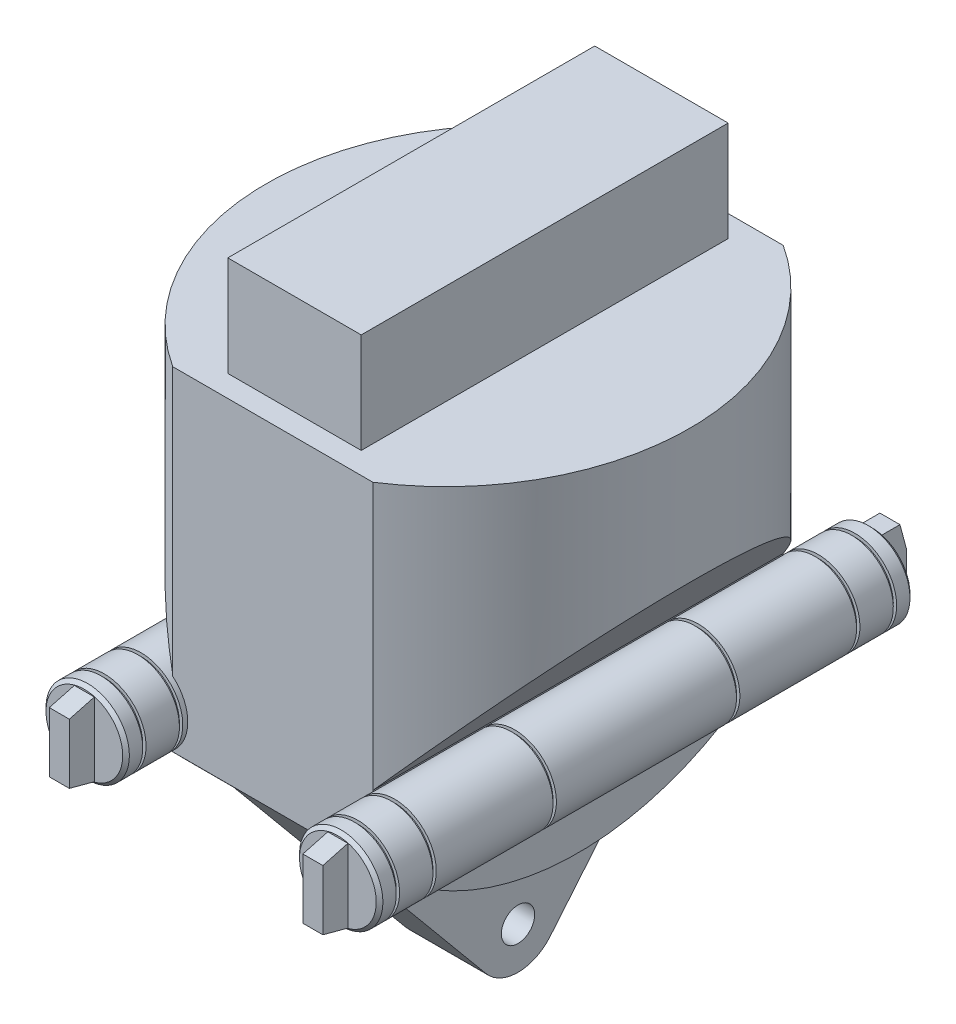
SolidWorks part; units mm, degrees
ref_plane "Front Plane" through (0, 0, 0) normal (0, 0, 1) x (1, 0, 0)
ref_plane "Top Plane" through (0, 0, 0) normal (0, 1, 0) x (1, 0, 0)
ref_plane "Right Plane" through (0, 0, 0) normal (1, 0, 0) x (0, 0, -1)
sketch "Sketch1" plane through (0, 0, 0) normal (1, 0, 0) x (0, 0, -1)
  line L1 (-61.5, 83.5) -> (61.5, 83.5)
  line L2 (-61.5, 83.5) -> (-61.5, -83.5)
  line L3 (-61.5, -83.5) -> (61.5, -83.5)
  line L4 (61.5, 83.5) -> (61.5, -83.5)
  line L5 (-61.5, 83.5) -> (61.5, -83.5) construction
  line L6 (-61.5, -83.5) -> (61.5, 83.5) construction
  point P0 (0, 0)
  dimension "D1" = 123
  dimension "D2" = 167
extrude "Boss-Extrude1" add sketch "Sketch1" along normal mid plane 127
sketch "Sketch2" plane through (0, 83.5, 0) normal (0, 1, 0) x (1, 0, 0)
  line L0 (0, 61.5) -> (0, -61.5) construction
  line L1 (63.5, 61.5) -> (-63.5, 61.5) construction
  line L2 (63.5, -61.5) -> (-63.5, -61.5) construction
  line L3 (-30, 61.5) -> (-30, -61.5) construction
  line L4 (-30, 61.5) -> (-63.5, 61.5)
  line L5 (-63.5, 61.5) -> (-63.5, -61.5)
  line L6 (-63.5, -61.5) -> (-30, -61.5)
  line L7 (63.5, -61.5) -> (30, -61.5)
  line L8 (30, 61.5) -> (63.5, 61.5)
  line L9 (63.5, 61.5) -> (63.5, -61.5)
  arc A0 (-30, 61.5) -> (-30, -61.5) centre (9.7015, 0) ccw
  arc A1 (30, 61.5) -> (30, -61.5) centre (-9.7015, 0) cw
  line M6 (-63.5, 61.5) -> (-63.5, -61.5)
  line M7 (-63.5, -61.5) -> (63.5, -61.5)
  line M8 (63.5, -61.5) -> (63.5, 61.5)
  line M9 (63.5, 61.5) -> (-63.5, 61.5)
  dimension "D2" = 73.2015
  dimension "D1" = 30
extrude "Cut-Extrude1" cut sketch "Sketch2" against normal through all contours A0 M9 M6 | A0 L5 M7 | A1 M8 M7 | A1 L9 M9 region at (-54.0203, 83.5, -46.9159) region at (-54.0203, 83.5, 46.9159) region at (54.0203, 83.5, -46.9159) region at (54.0203, 83.5, 46.9159)
sketch "Sketch3" plane through (0, 0, 61.5) normal (0, 0, 1) x (1, 0, 0)
  line L0 (0, 83.5) -> (0, -83.5) construction
  line L3 (30, 83.5) -> (-30, 83.5) construction
  line L4 (-12, -83.5) -> (-12, -43.5)
  line L5 (-12, -43.5) -> (-30, -43.5)
  line L6 (-30, -83.5) -> (-30, 83.5) construction
  line L7 (30, -83.5) -> (-30, -83.5) construction
  line L8 (-12, -83.5) -> (0, -83.5) construction
  line L9 (-30, -43.5) -> (-30, 3.5)
  line L10 (-30, 3.5) -> (-63.5, 43.5)
  line L11 (-63.5, 83.5) -> (-63.5, -83.5) construction
  line L12 (-63.5, 43.5) -> (-63.5, -83.5)
  line L13 (-63.5, -83.5) -> (-12, -83.5)
  line L14 (63.5, -83.5) -> (12, -83.5)
  line L15 (63.5, 43.5) -> (63.5, -83.5)
  line L16 (30, 3.5) -> (63.5, 43.5)
  line L17 (30, -43.5) -> (30, 3.5)
  line L18 (12, -43.5) -> (30, -43.5)
  line L19 (12, -83.5) -> (12, -43.5)
  dimension "D1" = 12
  dimension "D2" = 40
  dimension "D3" = 40
  dimension "D4" = 80
extrude "Cut-Extrude2" cut sketch "Sketch3" against normal through all
sketch "Sketch4" plane through (-30, 0, 0) normal (-1, 0, 0) x (0, 0, 1)
  line L0 (-61.5, -43.5) -> (-61.5, 3.5) construction
  line L1 (61.5, -43.5) -> (61.5, 3.5) construction
  line L2 (-61.5, -43.5) -> (61.5, -43.5) construction
  line L3 (-61.5, -16.5) -> (-61.5, -43.5)
  line L4 (-61.5, -43.5) -> (61.5, -43.5)
  line L5 (61.5, -43.5) -> (61.5, -16.5)
  arc A0 (-61.5, -16.5) -> (61.5, -16.5) centre (0, 40.0417) ccw
  point P9 (0, -43.5)
  line M1 (61.5, -43.5) -> (61.5, 3.5)
  line M3 (-61.5, 3.5) -> (-61.5, -43.5)
  line M4 (-61.5, -43.5) -> (61.5, -43.5)
  dimension "D1" = 20
extrude "Cut-Extrude3" cut sketch "Sketch4" against normal blind 18 contours A0 M3 M4 | A0 L4 M1 region at (-30, -35.6872, -46.6662) region at (-30, -35.6872, 46.6662)
mirror "Mirror1" about plane through (0, 0, 0) normal (1, 0, 0) of "Cut-Extrude3"
sketch "Sketch5" plane through (-12, 0, 0) normal (-1, 0, 0) x (0, 0, 1)
  line L0 (-61.5, -16.5) -> (-61.5, -83.5)
  line L1 (-61.5, -83.5) -> (61.5, -83.5)
  line L2 (61.5, -83.5) -> (61.5, -16.5)
  line L3 (0, -58.5) -> (0, -83.5) construction
  line L4 (-61.5, -16.5) -> (-9.617, -78.9852)
  line L5 (0, 0) -> (0, -71) construction
  line L6 (61.5, -16.5) -> (9.617, -78.9852)
  arc A0 (-9.617, -78.9852) -> (9.617, -78.9852) centre (0, -71) ccw
  circle A1 centre (0, -71) radius 5
  line M5 (61.5, -83.5) -> (61.5, -16.5)
  line M7 (-61.5, -16.5) -> (-61.5, -83.5)
  line M8 (-61.5, -83.5) -> (61.5, -83.5)
  dimension "D1" = 25
  dimension "D2" = 10
extrude "Cut-Extrude4" cut sketch "Sketch5" against normal through all contours A0 L4 M7 M8 | A0 L1 L6 M5 | A1 region at (-12, -61.2213, -42.8602) region at (-12, -61.2213, 42.8602) region at (-12, -71, 0)
sketch "Sketch6" plane through (0, 0, 0) normal (0, 0, 1) x (1, 0, 0)
  line L1 (30, 3.5) -> (30, 3.2345)
  line L2 (30, 3.5) -> (30, -16.5) construction
  line L6 (0, 83.5) -> (0, 0) construction
  line L7 (30, 83.5) -> (-30, 83.5) construction
  line L10 (-30, 3.5) -> (-30, 3.2345)
extrude "Boss-Extrude2" add sketch "Sketch6" along normal mid plane 40 separate body rebuild error yes
sketch "Sketch7" plane through (0, 0, 0) normal (0, 0, 1) x (1, 0, 0)
  circle A0 centre (38, -6.5) radius 12.5
  dimension "D1" = 25
extrude "Boss-Extrude3" add sketch "Sketch7" along normal mid plane 160
sketch "Sketch8" plane through (0, 0, 80) normal (0, 0, 1) x (1, 0, 0)
  line L1 (35, 4.5) -> (41, 4.5)
  line L2 (35, 4.5) -> (35, -17.5)
  line L3 (35, -17.5) -> (41, -17.5)
  line L4 (41, 4.5) -> (41, -17.5)
  line L5 (35, 4.5) -> (41, -17.5) construction
  line L6 (35, -17.5) -> (41, 4.5) construction
  point P0 (38, -6.5)
  dimension "D1" = 22
  dimension "D2" = 6
extrude "Boss-Extrude4" add sketch "Sketch8" along normal blind 7.5
ref_plane "Plane1" through (38, 0, 0) normal (1, 0, 0) x (0, 0, -1)
sketch "Sketch9" plane through (38, 0, 0) normal (1, 0, 0) x (0, 0, -1)
  line L0 (80, 6) -> (-80, 6) construction
  line L1 (-75, 6) -> (-74, 6)
  line L2 (-75, 6) -> (-75, 5)
  line L3 (-75, 5) -> (-74, 5)
  line L4 (-74, 6) -> (-74, 5)
  line L5 (-80, 6) -> (80, 6) construction
  line L6 (-64, 6) -> (-63, 6)
  line L7 (-64, 6) -> (-64, 5)
  line L8 (-64, 5) -> (-63, 5)
  line L9 (-63, 6) -> (-63, 5)
  line L10 (0, 6) -> (0, 0) construction
  line L11 (28, 5) -> (27, 5)
  line L12 (-28, 6) -> (-27, 6)
  line L13 (-28, 6) -> (-28, 5)
  line L14 (-28, 5) -> (-27, 5)
  line L15 (-27, 6) -> (-27, 5)
  line L16 (27, 6) -> (27, 5)
  line L17 (28, 6) -> (27, 6)
  line L18 (28, 6) -> (28, 5)
  line L19 (63, 6) -> (63, 5)
  line L20 (64, 6) -> (63, 6)
  line L21 (64, 5) -> (63, 5)
  line L22 (64, 6) -> (64, 5)
  line L23 (74, 6) -> (74, 5)
  line L24 (75, 6) -> (74, 6)
  line L25 (75, 6) -> (75, 5)
  line L26 (75, 5) -> (74, 5)
  line L27 (-80, -6.5) -> (80, -6.5) construction
  line L28 (-80, -17.5) -> (-80, 4.5) construction
  line L29 (80, -19) -> (80, 6) construction
  dimension "D1" = 1
  dimension "D2" = 10
  dimension "D3" = 5
  dimension "D4" = 35
revolve "Cut-Revolve1" cut sketch "Sketch9" angle 360 about L27
mirror "Mirror2" about plane through (0, 0, 0) normal (0, 0, 1) of "Boss-Extrude4"
chamfer "Chamfer1" distance 1 angle 45 2 edges at (50.5, -6.5, -80) (50.5, -6.5, 80)
chamfer "Chamfer2" distance 7.5 angle 15 4 edges at (38, -17.5, -87.5) (38, 4.5, -87.5) (38, -17.5, 87.5) (38, 4.5, 87.5) first distance on face at (38, -6.5, -87.5) first distance on face at (38, -17.5, 83.75) first distance on face at (38, 4.5, 83.75)
mirror "Mirror3" about plane through (0, 0, 0) normal (1, 0, 0) of "Cut-Revolve1", "Chamfer2", "Chamfer1", "Mirror2", "Boss-Extrude3", "Boss-Extrude4"
sketch "Sketch10" plane through (0, 83.5, 0) normal (0, 1, 0) x (1, 0, 0)
  line L1 (-20, 55) -> (20, 55)
  line L2 (-20, 55) -> (-20, -55)
  line L3 (-20, -55) -> (20, -55)
  line L4 (20, 55) -> (20, -55)
  line L5 (-20, 55) -> (20, -55) construction
  line L6 (-20, -55) -> (20, 55) construction
  point P0 (0, 0)
  dimension "D1" = 40
  dimension "D2" = 110
extrude "Boss-Extrude5" add sketch "Sketch10" along normal blind 30
scale "Scale1" bodies to scale 108 114 scale about centroid uniform scaling yes scale factor 0.333333
